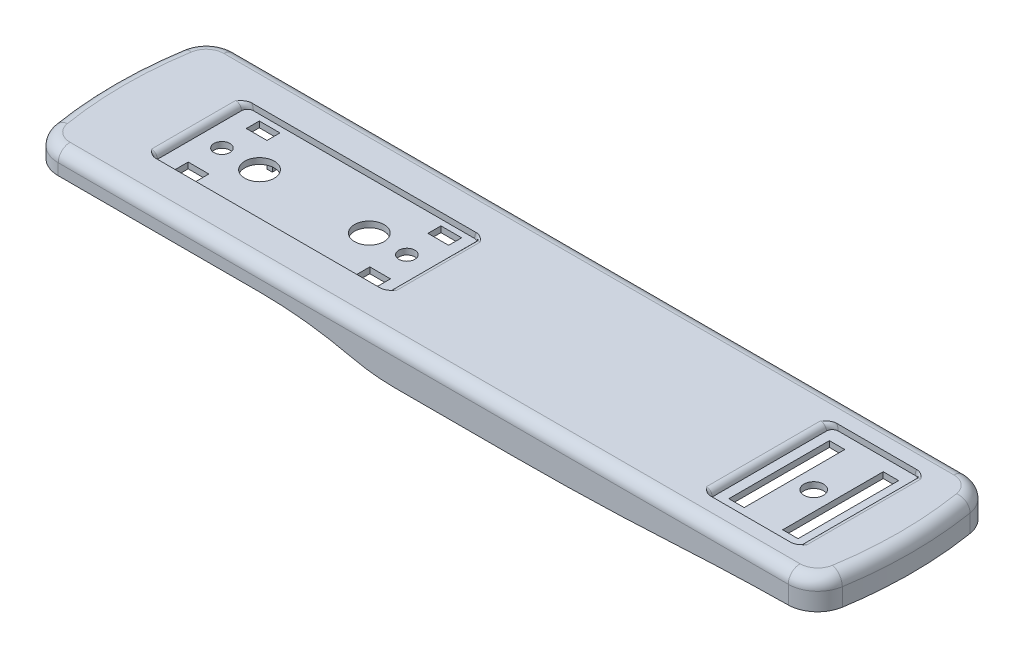
SolidWorks part; units mm, degrees
material "1023 Carbon Steel Sheet (SS)"
ref_plane "Front Plane" through (0, 0, 0) normal (0, 0, 1) x (1, 0, 0)
ref_plane "Top Plane" through (0, 0, 0) normal (0, 1, 0) x (1, 0, 0)
ref_plane "Right Plane" through (0, 0, 0) normal (1, 0, 0) x (0, 0, -1)
ref_axis "X-axis" through (-88.99, 0, 0) along (1, 0, 0)
ref_axis "Y-axis" through (0, -55, 0) along (0, 1, 0)
ref_axis "Z-axis" through (0, 0, 55) along (0, 0, -1)
sketch "Sketch1" plane through (0, 0, 0) normal (0, 1, 0) x (1, 0, 0)
  line L1 (-83.5815, -19.05) -> (83.5815, -19.05)
  line L3 (-83.5815, 19.05) -> (83.5815, 19.05)
  line L5 (-83.5815, -19.05) -> (83.5815, 19.05) construction
  line L6 (-83.5815, 19.05) -> (83.5815, -19.05) construction
  arc A0 (83.5815, 19.05) -> (83.5815, -19.05) centre (0, 0) cw
  arc A1 (-83.5815, -19.05) -> (-83.5815, 19.05) centre (0, 0) cw
  point P0 (0, 0)
  point P8 (-85.725, 0)
  point P9 (85.725, 0)
  dimension "D1" = 38.1
  dimension "D2" = 171.45
extrude "Boss-Extrude1" add sketch "Sketch1" along normal blind 8.255
fillet "Fillet1" radius 6.35 4 edges at (83.5815, 4.1275, -19.05) (83.5815, 4.1275, 19.05) (-83.5815, 4.1275, -19.05) (-83.5815, 4.1275, 19.05)
fillet "Fillet2" radius 2.54 8 edges at (-82.4677, 8.255, 17.536) (-85.725, 8.255, 0) (-82.4677, 8.255, -17.536) (0, 8.255, -19.05) (82.4677, 8.255, -17.536) (85.725, 8.255, 0) (82.4677, 8.255, 17.536) (0, 8.255, 19.05)
sketch "Sketch2" plane through (0, 0, 0) normal (0, 0, 1) x (1, 0, 0)
  line L1 (85.725, 0) -> (85.725, 1.905)
  line L2 (85.725, 0) -> (85.725, 5.715) construction
  line L3 (-34.925, 3.302) -> (-85.725, 3.302)
  line L4 (-85.725, 5.715) -> (-85.725, 0) construction
  line L5 (-85.725, 3.302) -> (-85.725, 0)
  line L6 (-78.3524, 8.255) -> (78.3524, 8.255) construction
  line L7 (-78.3524, 0) -> (78.3524, 0) construction
  line L8 (19.1736, 0) -> (-6.2264, 0)
  line L9 (-78.3524, 8.255) -> (-82.1133, 8.255) construction
  arc A0 (85.725, 1.905) -> (54.4869, 1.0108) centre (85.725, -544.195) ccw
  arc A2 (-6.2264, 0) -> (-15.6003, 1.0785) centre (-6.2264, 41.275) cw
  arc A3 (-15.6003, 1.0785) -> (-34.925, 3.302) centre (-34.925, -81.788) ccw
  arc A4 (54.4869, 1.0108) -> (19.1736, 0) centre (19.1736, 617.342) cw
  dimension "D1" = 6.35
  dimension "D5" = 41.275
  dimension "D6" = 85.09
  dimension "D7" = 546.1
  dimension "D2" = 50.8
  dimension "D3" = 4.953
  dimension "D4" = 25.4
extrude "Cut-Extrude1" cut sketch "Sketch2" against normal through all both and the other way through all
sketch "Sketch3" plane through (0, 8.255, 0) normal (0, 1, 0) x (1, 0, 0)
  line L0 (-5.9071, 0) -> (5.9071, 0) construction
  line L1 (-67.0814, -10.2997) -> (-17.0434, -10.2997)
  line L2 (-67.0814, -10.2997) -> (-67.0814, 10.2997)
  line L3 (-67.0814, 10.2997) -> (-17.0434, 10.2997)
  line L4 (-17.0434, -10.2997) -> (-17.0434, 10.2997)
  line L5 (-67.0814, -10.2997) -> (-17.0434, 10.2997) construction
  line L6 (-67.0814, 10.2997) -> (-17.0434, -10.2997) construction
  arc A0 (-84.6206, 13.716) -> (-84.6206, -13.716) centre (0, 0) ccw construction
  point P0 (-42.0624, 0)
  point P10 (-85.725, 0)
  dimension "D1" = 50.038
  dimension "D2" = 20.5994
  dimension "D3" = 18.6436
extrude "Cut-Extrude2" cut sketch "Sketch3" against normal blind 1.27
sketch "Sketch4" plane through (0, 8.255, 0) normal (0, 1, 0) x (1, 0, 0)
  line L0 (-5.9071, 0) -> (5.9071, 0) construction
  line L1 (55.245, -13.5255) -> (74.295, -13.5255)
  line L2 (55.245, -13.5255) -> (55.245, 13.5255)
  line L3 (55.245, 13.5255) -> (74.295, 13.5255)
  line L4 (74.295, -13.5255) -> (74.295, 13.5255)
  line L5 (55.245, -13.5255) -> (74.295, 13.5255) construction
  line L6 (55.245, 13.5255) -> (74.295, -13.5255) construction
  arc A0 (84.6206, -13.716) -> (84.6206, 13.716) centre (0, 0) ccw construction
  point P0 (64.77, 0)
  point P11 (85.725, 0)
  dimension "D1" = 19.05
  dimension "D2" = 27.051
  dimension "D3" = 11.43
extrude "Cut-Extrude3" cut sketch "Sketch4" against normal up to surface (1.27 mm away) up to face at (-42.0624, 6.985, 0)
shell "Shell2" thickness 1.27 removed face at (-66.4771, 3.302, 0) removed face at (-25.2308, 2.4673, 0) removed face at (-10.9288, 0.4049, 0) removed face at (6.4736, 0, 0) removed face at (36.8339, 0.3791, 0) removed face at (72.8115, 1.6387, -2.2444)
fillet "Fillet4" radius 1.27 4 edges at (-67.0814, 8.255, 0) (55.245, 8.255, 0) (-17.0434, 8.255, 0) (74.295, 8.255, 0)
fillet "Fillet3" radius 1.27 8 edges at (74.667, 7.883, 13.5255) (74.667, 7.883, -13.5255) (54.873, 7.883, -13.5255) (54.873, 7.883, 13.5255) (-67.4534, 7.883, 10.2997) (-16.6714, 7.883, 10.2997) (-16.6714, 7.883, -10.2997) (-67.4534, 7.883, -10.2997)
fillet "Fillet5" radius 1.27 4 edges at (-68.3514, 5.715, 0) (-15.7734, 5.715, 0) (75.565, 5.715, 0) (53.975, 5.715, 0)
sketch "Sketch6" plane through (0, 5.715, 0) normal (0, -1, 0) x (1, 0, 0)
  line L1 (57.3405, -10.795) -> (60.6425, -10.795)
  line L2 (57.3405, -10.795) -> (57.3405, 10.795)
  line L3 (57.3405, 10.795) -> (60.6425, 10.795)
  line L4 (60.6425, -10.795) -> (60.6425, 10.795)
  line L5 (57.3405, -10.795) -> (60.6425, 10.795) construction
  line L6 (57.3405, 10.795) -> (60.6425, -10.795) construction
  line L7 (5.9071, 0) -> (-5.9071, 0) construction
  line L8 (68.8975, -10.795) -> (72.1995, -10.795)
  line L9 (68.8975, -10.795) -> (68.8975, 10.795)
  line L10 (68.8975, 10.795) -> (72.1995, 10.795)
  line L11 (72.1995, -10.795) -> (72.1995, 10.795)
  line L12 (68.8975, -10.795) -> (72.1995, 10.795) construction
  line L13 (68.8975, 10.795) -> (72.1995, -10.795) construction
  line L14 (57.3405, 0) -> (53.975, 0) construction
  line L15 (53.975, -14.7955) -> (53.975, 14.7955) construction
  line L16 (72.1995, 0) -> (75.565, 0) construction
  line L17 (75.565, 14.7955) -> (75.565, -14.7955) construction
  point P0 (58.9915, 0)
  point P10 (70.5485, 0)
  dimension "D2" = 3.302
  dimension "D3" = 21.59
  dimension "D4" = 8.255
extrude "Cut-Extrude4" cut sketch "Sketch6" against normal through all
sketch "Sketch7" plane through (0, 5.715, 0) normal (0, -1, 0) x (1, 0, 0)
  line L1 (72.1995, 10.795) -> (73.3425, 10.795)
  line L2 (72.1995, 10.795) -> (72.1995, 8.255)
  line L3 (72.1995, 8.255) -> (73.3425, 8.255)
  line L4 (73.3425, 10.795) -> (73.3425, 8.255)
  line L5 (72.1995, -10.795) -> (73.3425, -10.795)
  line L6 (72.1995, -10.795) -> (72.1995, -8.255)
  line L7 (72.1995, -8.255) -> (73.3425, -8.255)
  line L8 (73.3425, -10.795) -> (73.3425, -8.255)
  dimension "D1" = 1.143
  dimension "D2" = 2.54
extrude "Boss-Extrude2" add sketch "Sketch7" along normal blind 3.175
sketch "Sketch8" plane through (0, 5.715, 0) normal (0, -1, 0) x (1, 0, 0)
  line L0 (-15.7734, 11.5697) -> (-15.7734, -11.5697) construction
  line L1 (-19.8374, 9.0297) -> (-24.2824, 9.0297)
  line L2 (-19.8374, 9.0297) -> (-19.8374, 6.2357)
  line L3 (-19.8374, 6.2357) -> (-24.2824, 6.2357)
  line L4 (-24.2824, 9.0297) -> (-24.2824, 6.2357)
  line L5 (-67.0814, 11.5697) -> (-17.0434, 11.5697) construction
  line L6 (5.9071, 0) -> (-5.9071, 0) construction
  line L7 (-24.2824, -9.0297) -> (-24.2824, -6.2357)
  line L8 (-19.8374, -6.2357) -> (-24.2824, -6.2357)
  line L9 (-19.8374, -9.0297) -> (-19.8374, -6.2357)
  line L10 (-19.8374, -9.0297) -> (-24.2824, -9.0297)
  line L11 (-68.3514, -11.5697) -> (-68.3514, 11.5697) construction
  line L12 (-63.2714, 9.0297) -> (-58.8264, 9.0297)
  line L13 (-63.2714, 9.0297) -> (-63.2714, 6.2357)
  line L14 (-63.2714, 6.2357) -> (-58.8264, 6.2357)
  line L15 (-58.8264, 9.0297) -> (-58.8264, 6.2357)
  line L16 (-63.2714, -9.0297) -> (-63.2714, -6.2357)
  line L17 (-63.2714, -9.0297) -> (-58.8264, -9.0297)
  line L18 (-58.8264, -9.0297) -> (-58.8264, -6.2357)
  line L19 (-63.2714, -6.2357) -> (-58.8264, -6.2357)
  dimension "D1" = 4.064
  dimension "D2" = 2.794
  dimension "D3" = 4.445
  dimension "D4" = 2.54
  dimension "D5" = 5.08
  dimension "D6" = 2.54
extrude "Cut-Extrude5" cut sketch "Sketch8" against normal through all
sketch "Sketch9" plane through (0, 5.715, 0) normal (0, -1, 0) x (1, 0, 0)
  line L2 (-63.2714, 9.0297) -> (-63.2714, -9.0297) construction
  line L3 (-24.2824, -9.0297) -> (-24.2824, 9.0297) construction
  line L4 (-67.0814, -9.0297) -> (-67.0814, 9.0297) construction
  circle A0 centre (-22.5679, 0) radius 1.7145
  circle A1 centre (-30.6324, 0) radius 3.175
  circle A2 centre (-54.1909, 0) radius 3.175
  circle A3 centre (-62.2554, 0) radius 1.7145
  point P8 (-63.2714, 0)
  point P9 (-24.2824, 0)
  dimension "D1" = 3.429
  dimension "D2" = 6.35
  dimension "D4" = 3.175
  dimension "D5" = 4.826
  dimension "D3" = 3.175
extrude "Cut-Extrude6" cut sketch "Sketch9" against normal through all
sketch "Sketch10" plane through (0, 5.715, 0) normal (0, -1, 0) x (1, 0, 0)
  line L0 (-63.2714, 6.2357) -> (-58.8264, 6.2357) construction
  line L1 (-58.8264, 9.0297) -> (-57.6834, 9.0297)
  line L2 (-58.8264, 9.0297) -> (-58.8264, 6.2357)
  line L3 (-58.8264, 6.2357) -> (-57.6834, 6.2357)
  line L4 (-57.6834, 9.0297) -> (-57.6834, 6.2357)
  dimension "D1" = 1.143
extrude "Boss-Extrude3" add sketch "Sketch10" along normal blind 4.064
mirror "Mirror1" about plane through (0, 0, 0) normal (0, 0, 1) of "Boss-Extrude3"
pattern_linear "LPattern1" count 2 spacing 38.989 along (1, 0, 0) of "Mirror1"
sketch "Sketch11" plane through (0, 5.715, 0) normal (0, -1, 0) x (1, 0, 0)
  line L1 (-88.99, 0) -> (88.99, 0) construction
  line L2 (60.6425, 0) -> (68.8975, 0) construction
  line L3 (60.6425, -10.795) -> (60.6425, 10.795) construction
  line L4 (68.8975, 10.795) -> (68.8975, -10.795) construction
  circle A0 centre (64.77, 0) radius 2.0955
  dimension "D1" = 4.191
extrude "Cut-Extrude7" cut sketch "Sketch11" against normal through all
